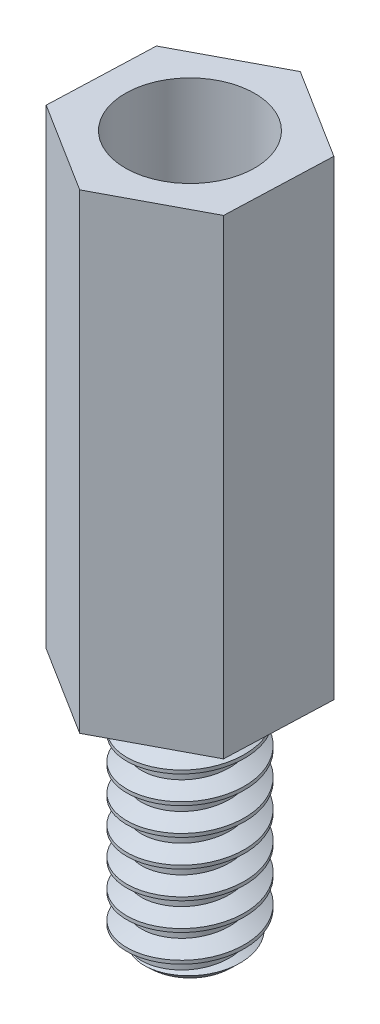
SolidWorks part; units mm, degrees
ref_plane "Front Plane" through (0, 0, 0) normal (0, 0, 1) x (1, 0, 0)
ref_plane "Top Plane" through (0, 0, 0) normal (0, 1, 0) x (1, 0, 0)
ref_plane "Right Plane" through (0, 0, 0) normal (1, 0, 0) x (0, 0, -1)
sketch "Sketch1" plane through (0, 0, 0) normal (0, 1, 0) x (1, 0, 0)
  line L1 (2.2983, -1.4426) -> (2.3985, 1.2691)
  line L2 (2.3985, 1.2691) -> (0.1002, 2.7117)
  line L3 (0.1002, 2.7117) -> (-2.2983, 1.4426)
  line L4 (-2.2983, 1.4426) -> (-2.3985, -1.2691)
  line L5 (-2.3985, -1.2691) -> (-0.1002, -2.7117)
  line L6 (-0.1002, -2.7117) -> (2.2983, -1.4426)
  circle A0 centre (0, 0) radius 2.35 construction
  dimension "D1" = 4.7
extrude "Boss-Extrude1" add sketch "Sketch1" along normal blind 12
hole_wizard "M4 Tapped Hole1" positions "Sketch2" profile "Sketch3" tap size "M4" standard "DIN"
sketch "Sketch2" plane through (0, 12, 0) normal (0, 1, 0) x (1, 0, 0)
  point P0 (0, 0)
sketch "Sketch3" plane through (0, 12, 0) normal (1, 0, 0) x (0, 0, 1)
  line L0 (0, 0) -> (0, 6.9914)
  line L1 (0, 6.9914) -> (1.65, 6)
  line L2 (1.65, 6) -> (1.65, 0)
  line L5 (1.65, 0) -> (0, 0)
  line L10 (0, 6.9914) -> (-1.65, 6) construction
  line L11 (0, -6.35) -> (0, 107.95) construction
  dimension "Tap Drill Dia." = 3.3
  dimension "Tap Drill Depth" = 6
  dimension "Drill Angle" = 118
cosmetic thread "Hole Thread1" parameters "D1"=6, "D2"=4
sketch "Sketch4" plane through (0, 0, 0) normal (0, -1, 0) x (1, 0, 0)
  circle A0 centre (0, 0) radius 1.5
  dimension "D1" = 3
extrude "Boss-Extrude2" add sketch "Sketch4" along normal blind 6
fillet "Fillet1" radius 0.5 1 edges at (0, -6, -1.5) conic radius 10
thread "Thread1" pitch 0.7 method cut profile "Thread Profile1" start angle 0, offset 0, length 0, pitch 0.7, diameter 3
ref_plane "Plane1" through (-1.5, 0, 0) normal (0, 0, 1) x (-1, 0, 0)
sketch "Thread Profile1" plane through (-1.5, 0, 0) normal (0, 0, 1) x (-1, 0, 0)
  line L0 (0, 0) -> (0, 0.7) construction
  line L11 (0, 0) -> (0, 0.6125)
  line L12 (0, 0.6125) -> (-0.3789, 0.3937)
  line L13 (-0.3789, 0.3937) -> (-0.3789, 0.2187)
  line L15 (-0.3789, 0.2187) -> (0, 0)
  line L17 (-0.3789, 0.3062) -> (0, 0.3062) construction
  point P2 (0, 0)
  dimension "Pitch" = 0.7
  dimension "Profile_Angle" = 60
  dimension "Profile_Land" = 0.175
  dimension "Profile_Height" = 0.3789
